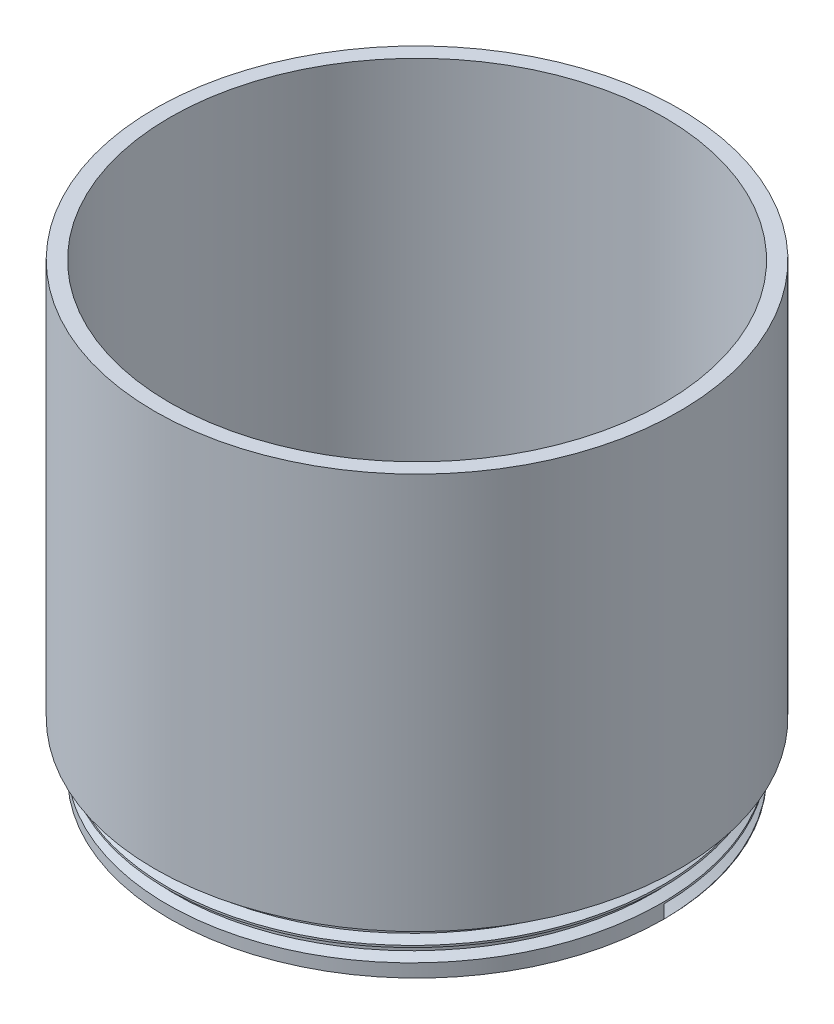
SolidWorks part; units mm, degrees
ref_plane "Front Plane" through (0, 0, 0) normal (0, 0, 1) x (1, 0, 0)
ref_plane "Top Plane" through (0, 0, 0) normal (0, 1, 0) x (1, 0, 0)
ref_plane "Right Plane" through (0, 0, 0) normal (1, 0, 0) x (0, 0, -1)
sketch "Sketch1" plane through (0, 0, 0) normal (0, 1, 0) x (1, 0, 0)
  circle A0 centre (0, 0) radius 30.25
  circle A1 centre (0, 0) radius 32.75
  dimension "D1" = 65.5
  dimension "D2" = 60.5
extrude "Boss-Extrude1" add sketch "Sketch1" along normal blind 6.75
sketch "Sketch2" plane through (0, 6.75, 0) normal (0, 1, 0) x (1, 0, 0)
  circle A0 centre (0, 0) radius 34.75
  circle A1 centre (0, 0) radius 30.25
  circle A2 centre (0, 0) radius 30.25 construction
  dimension "D1" = 69.5
extrude "Boss-Extrude2" add sketch "Sketch2" along normal blind 2.5
thread "Thread1" pitch 2 method cut profile "Thread Profile1" start angle 0, offset 0, length 5, pitch 2, diameter 65.5
ref_plane "Plane1" through (32.75, 0, 0) normal (0, 0, 1) x (1, 0, 0)
sketch "Thread Profile1" plane through (32.75, 0, 0) normal (0, 0, 1) x (1, 0, 0)
  line L0 (0, 0) -> (0, 2) construction
  line L11 (0, 0) -> (0, 1.75)
  line L12 (0, 1.75) -> (-1.0825, 1.125)
  line L13 (-1.0825, 1.125) -> (-1.0825, 0.625)
  line L15 (-1.0825, 0.625) -> (0, 0)
  line L17 (-1.0825, 0.875) -> (0, 0.875) construction
  point P2 (0, 0)
  dimension "Pitch" = 2
  dimension "Profile_Angle" = 60
  dimension "Profile_Land" = 0.5
  dimension "Profile_Height" = 1.0825
sketch "Sketch3" plane through (0, 0, 0) normal (0, -1, 0) x (1, 0, 0)
  line L0 (44.8559, 0) -> (-42.1978, 0) construction
  line L1 (0, 62.0673) -> (0, -60.7383) construction
  line L2 (0, 0) -> (47.1609, 47.1609) construction
  line L3 (0, 0) -> (-47.1609, 47.1609) construction
  line L4 (0, 0) -> (-47.1609, -47.1609) construction
  line L5 (0, 0) -> (47.1609, -47.1609) construction
  line L6 (19.2687, 19.2687) -> (21.39, 21.39)
  line L7 (19.2687, -19.2687) -> (21.39, -21.39)
  line L8 (-19.2687, 19.2687) -> (-21.39, 21.39)
  line L9 (-19.2687, -19.2687) -> (-21.39, -21.39)
  arc A0 (-21.39, 21.39) -> (-21.39, -21.39) centre (0, 0) ccw
  arc A1 (-19.2687, 19.2687) -> (-19.2687, -19.2687) centre (0, 0) ccw
  circle A2 centre (0, 0) radius 30.25 construction
  arc A3 (19.2687, -19.2687) -> (19.2687, 19.2687) centre (0, 0) ccw
  arc A4 (21.39, -21.39) -> (21.39, 21.39) centre (0, 0) ccw
  dimension "D1" = 3
  dimension "D2" = 45
extrude "Boss-Extrude3" add sketch "Sketch3" against normal blind 2
sketch "Sketch4" plane through (0, 0, 0) normal (0, -1, 0) x (1, 0, 0)
  circle A0 centre (0, 0) radius 31.25
sketch "Sketch5" plane through (0, 9.25, 0) normal (0, 1, 0) x (1, 0, 0)
  circle A0 centre (0, 0) radius 34.75
  circle A2 centre (0, 0) radius 34.75 construction
  circle A3 centre (0, 0) radius 32.75
  dimension "D1" = 2
extrude "Boss-Extrude4" add sketch "Sketch5" along normal blind 50
